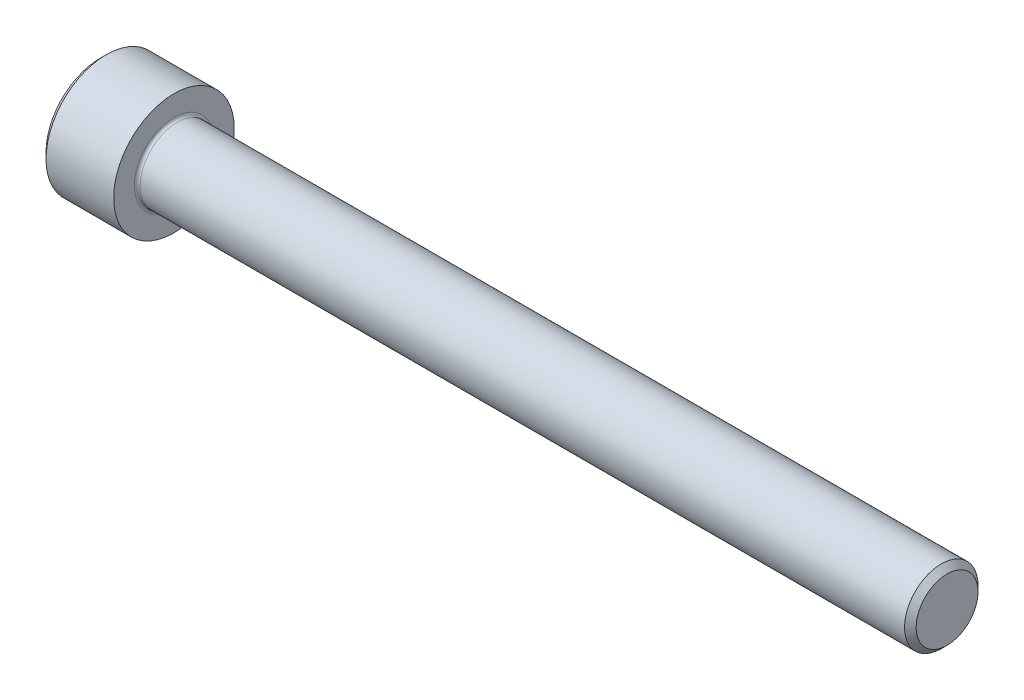
SolidWorks part; units mm, degrees
material "Alloy Steel"
ref_plane "Z Plane" through (0, 0, 0) normal (0, 0, 1) x (1, 0, 0)
ref_plane "Y Plane" through (0, 0, 0) normal (0, 1, 0) x (1, 0, 0)
ref_plane "X Plane" through (0, 0, 0) normal (1, 0, 0) x (0, 0, -1)
sketch "Sketch1" plane through (0, 0, 0) normal (0, 1, 0) x (1, 0, 0)
  line L0 (0, 3.9624) -> (0, -3.9624) construction
  line L1 (0, 0) -> (0, 3.9624)
  line L2 (0, 3.9624) -> (4.826, 3.9624)
  line L3 (4.826, 3.9624) -> (4.826, 2.413)
  line L4 (4.826, 2.413) -> (55.626, 2.413)
  line L5 (55.626, 2.413) -> (55.626, -2.413) construction
  line L6 (55.626, 2.413) -> (55.626, 0)
  line L7 (55.626, 0) -> (0, 0)
  line L8 (0, -3.9624) -> (1.6087, -3.9624) construction
  line L9 (1.6087, -3.9624) -> (3.2173, -3.9624) construction
  line L10 (3.2173, -3.9624) -> (4.826, -3.9624) construction
  point P2 (0, 0)
  point P5 (55.626, 0)
  dimension "Head Diameter" = 7.9248
  dimension "Thread Diameter" = 4.826
  dimension "Thread Length" = 50.8
revolve "Body" add sketch "Sketch1" angle 360 about L7
ref_plane "Plane1" through (3.2173, 0, 0) normal (1, 0, 0) x (0, 0, -1)
sketch "Sketch2" plane through (0, 0, 0) normal (-1, 0, 0) x (0, 0, 1)
  line L1 (-2.2914, 0) -> (-1.1457, -1.9844)
  line L2 (-1.1457, -1.9844) -> (1.1457, -1.9844)
  line L3 (1.1457, -1.9844) -> (2.2914, 0)
  line L4 (2.2914, 0) -> (1.1457, 1.9844)
  line L5 (1.1457, 1.9844) -> (-1.1457, 1.9844)
  line L6 (-1.1457, 1.9844) -> (-2.2914, 0)
  circle A0 centre (0, 0) radius 1.9844 construction
  dimension "Hex Head" = 3.9688
extrude "Hex" cut sketch "Sketch2" against normal up to surface (3.2173 mm away) up to plane "Plane1"
chamfer "Chamfer1" distance 0.381 angle 45 2 edges at (55.626, 0, -2.413) (0, 0, -3.9624)
fillet "Fillet1" radius 0.1905 1 edges at (4.826, 0, -2.413)
sketch "Sketch3" plane through (0, 0, 0) normal (1, 0, 0) x (0, 0, -1)
  circle A0 centre (0, 0) radius 2.2914
extrude "Hex Chamfer" cut sketch "Sketch3" along normal blind 2.54 draft 45
